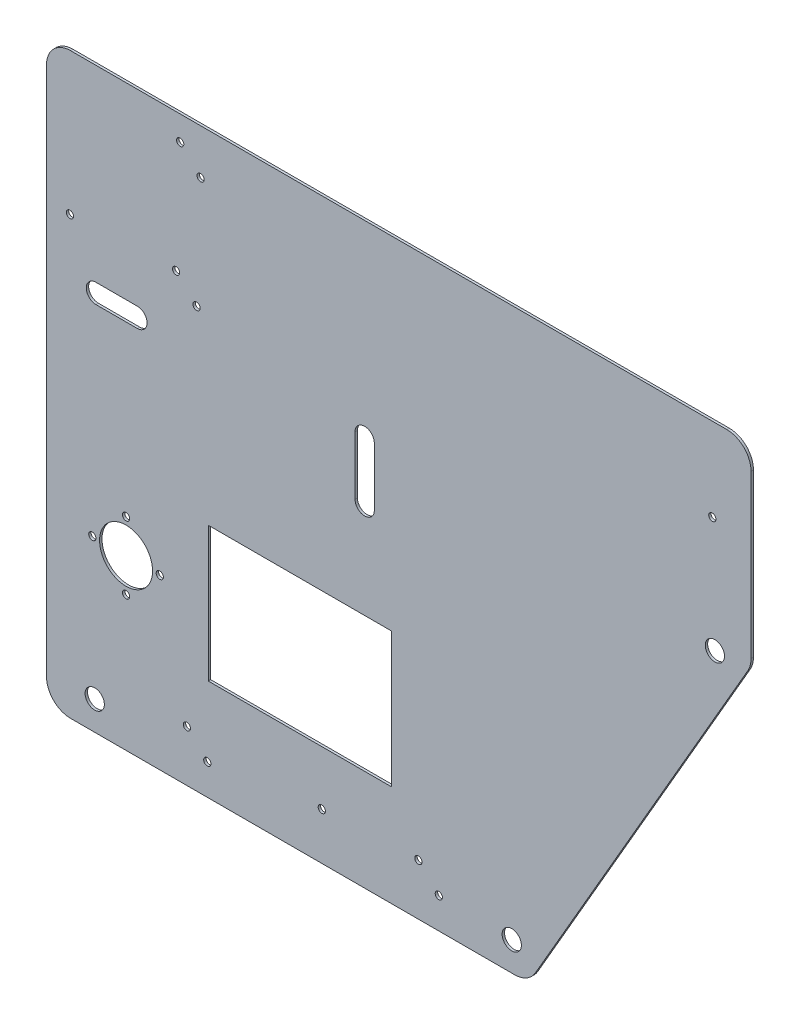
SolidWorks part; units mm, degrees
ref_plane "Front Plane" through (0, 0, 0) normal (0, 0, 1) x (1, 0, 0)
ref_plane "Top Plane" through (0, 0, 0) normal (0, 1, 0) x (1, 0, 0)
ref_plane "Right Plane" through (0, 0, 0) normal (1, 0, 0) x (0, 0, -1)
sketch "Sketch1" plane through (0, 0, 0) normal (0, 0, 1) x (1, 0, 0)
  line L0 (100, 80) -> (192.376, 80)
  line L1 (-100, -80) -> (100, -80)
  line L2 (-100, -80) -> (-100, 80)
  line L3 (-100, 80) -> (100, 80)
  line L4 (100, -80) -> (100, 80)
  line L5 (-100, -80) -> (100, 80) construction
  line L6 (-100, 80) -> (100, -80) construction
  line L7 (192.376, 80) -> (100, -80)
  line L8 (100, 80) -> (100, -80)
  line L10 (-100, 80) -> (192.376, 80)
  line L11 (-100, 80) -> (-100, 110)
  line L12 (-100, 110) -> (192.376, 110)
  line L13 (192.376, 80) -> (192.376, 110)
  point P0 (0, 0)
  dimension "D1" = 160
  dimension "D2" = 200
  dimension "D3" = 30
  dimension "D4" = 30
extrude "Boss-Extrude1" add sketch "Sketch1" along normal blind 1 contours L1 L4 L3 L2 | L7 L0 L4 | L11 L10 L13 L12 region at (0, 0, 0) region at (130.792, 26.6667, 0)
sketch "Sketch2" plane through (0, 0, 1) normal (0, 0, 1) x (1, 0, 0)
  line L0 (-100, -80) -> (100, -80) construction
  line L1 (192.376, 80) -> (100, -80) construction
  line L2 (-100, -80) -> (-100, 110) construction
  line L3 (-100, 110) -> (192.376, 110) construction
  line L4 (-79.5166, 78) -> (-62.3003, 78) construction
  line L7 (-100, -80) -> (-100, 110) construction
  line L8 (-29.8584, 15) -> (-29.8584, -35) construction
  line L9 (-79.5166, 82) -> (-62.3003, 82)
  line L10 (-79.5166, 74) -> (-62.3003, 74)
  line L11 (-32.8584, 18) -> (43.1416, 18)
  line L12 (-32.8584, 18) -> (-32.8584, -38)
  line L13 (-32.8584, -38) -> (43.1416, -38)
  line L14 (43.1416, 18) -> (43.1416, -38)
  line L15 (20.1416, 15) -> (-29.8584, 15) construction
  line L17 (40.1416, -35) -> (40.1416, 15) construction
  line L18 (32.0262, 82) -> (32.0262, 57.7776) construction
  line L19 (36.0262, 82) -> (36.0262, 57.7776)
  line L20 (28.0262, 82) -> (28.0262, 57.7776)
  circle A0 centre (93.0718, -68) radius 4
  circle A1 centre (177.3649, 78) radius 4
  circle A2 centre (-67, -10) radius 11
  circle A3 centre (-80, -68) radius 4
  circle A4 centre (-53, -10) radius 1.5
  circle A5 centre (-67, 4) radius 1.5
  circle A6 centre (-81, -10) radius 1.5
  circle A7 centre (-67, -24) radius 1.5
  circle A10 centre (32.0262, 70) radius 4 construction
  arc A11 (-79.5166, 82) -> (-79.5166, 74) centre (-79.5166, 78) ccw
  arc A12 (-62.3003, 74) -> (-62.3003, 82) centre (-62.3003, 78) ccw
  circle A32 centre (62.7961, -67.2426) radius 1.5
  circle A33 centre (54.3108, -58.7574) radius 1.5
  circle A34 centre (-33.2742, -67.2426) radius 1.5
  circle A35 centre (-41.7595, -58.7574) radius 1.5
  circle A36 centre (14.2259, -60.5) radius 1.5
  circle A37 centre (-37.7547, 94.2817) radius 1.5
  circle A38 centre (-46.24, 102.767) radius 1.5
  circle A39 centre (-90.2956, 101.0243) radius 1.5
  circle A40 centre (176.3056, 125.4889) radius 1.5
  arc A41 (36.0262, 82) -> (28.0262, 82) centre (32.0262, 82) ccw
  arc A42 (28.0262, 57.7776) -> (36.0262, 57.7776) centre (32.0262, 57.7776) ccw
  point P12 (-70.9085, 78)
  point P65 (32.0262, 69.8888)
  point P70 (0, 0)
  dimension "D3" = 8
  dimension "D4" = 8
  dimension "D9" = 22
  dimension "D10" = 8
  dimension "D12" = 3
  dimension "D13" = 3
  dimension "D14" = 3
  dimension "D15" = 3
  dimension "D16" = 14
  dimension "D20" = 4
  dimension "D22" = 8
  dimension "D23" = 3
  dimension "D24" = 20
  dimension "D25" = 3
  dimension "D1" = 12
  dimension "D2" = 12
  dimension "D5" = 32
  dimension "D6" = 12
  dimension "D7" = 33
  dimension "D8" = 70
  dimension "D11" = 12
  dimension "D17" = 14
  dimension "D18" = 14
  dimension "D19" = 14
  dimension "D21" = 40
  dimension "D26" = 3
  dimension "D27" = 3
  dimension "D28" = 8
  dimension "D29" = 3
extrude "Cut-Extrude1" cut sketch "Sketch2" against normal blind 3
sketch "Sketch3" plane through (0, 0, 1) normal (0, 0, 1) x (1, 0, 0)
  line L0 (192.376, 80) -> (192.376, 110) construction
  line L1 (-100, 110) -> (192.376, 110)
  line L2 (-100, 110) -> (-100, 160)
  line L3 (-100, 160) -> (192.376, 160)
  line L4 (192.376, 110) -> (192.376, 160)
  dimension "D1" = 50
extrude "Boss-Extrude2" add sketch "Sketch3" against normal blind 1
fillet "Fillet1" radius 10 5 edges at (100, -80, 0.5) (-100, -80, 0.5) (-100, 160, 0.5) (192.376, 160, 0.5) (192.376, 80, 0.5)
sketch "Sketch4" plane through (0, 0, 1) normal (0, 0, 1) x (1, 0, 0)
  circle A2 centre (-44.5363, 149.8294) radius 1.5
  circle A3 centre (-36.051, 141.3442) radius 1.5
  circle A4 centre (176.3056, 125.4889) radius 1.5
  dimension "D1" = 3
extrude "Cut-Extrude2" cut sketch "Sketch4" against normal blind 11
